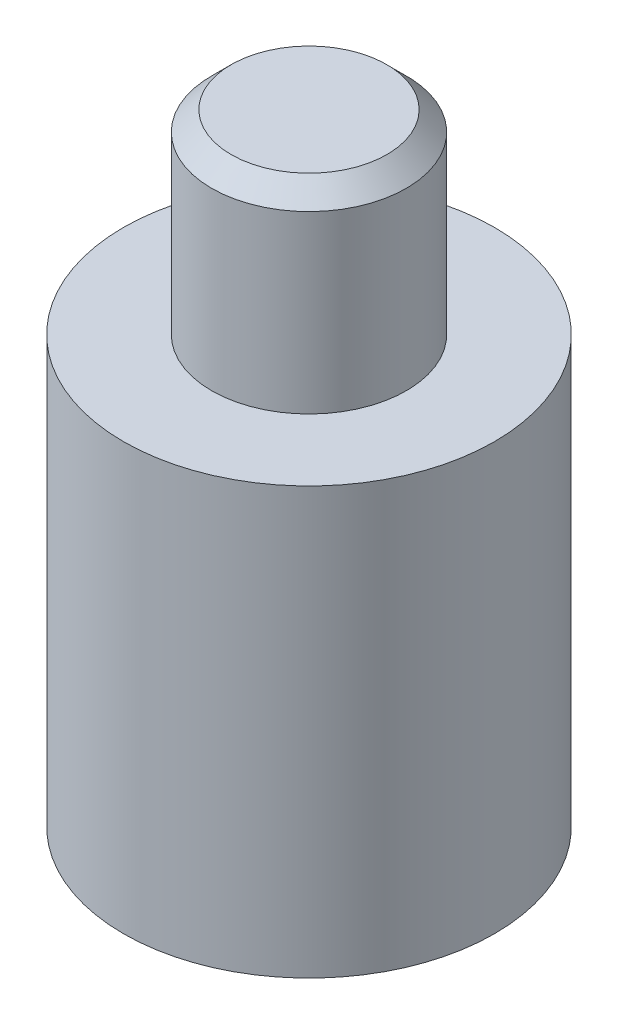
SolidWorks part; units mm, degrees
ref_plane "Front Plane" through (0, 0, 0) normal (0, 0, 1) x (1, 0, 0)
ref_plane "Top Plane" through (0, 0, 0) normal (0, 1, 0) x (1, 0, 0)
ref_plane "Right Plane" through (0, 0, 0) normal (1, 0, 0) x (0, 0, -1)
sketch "Sketch1" plane through (0, 0, 0) normal (0, 1, 0) x (1, 0, 0)
  circle A0 centre (0, 0) radius 1.5
  circle A1 centre (0, 0) radius 4.7625
extrude "Boss-Extrude1" add sketch "Sketch1" along normal blind 10.9409 contours A1 A0 | A0 region at (0, 0, 0) region at (-4.6278, 0, 0)
sketch "Sketch2" plane through (0, 10.9409, 0) normal (0, 1, 0) x (1, 0, 0)
  circle A0 centre (0, 0) radius 2.5
extrude "Boss-Extrude2" add sketch "Sketch2" along normal blind 5
extrude "Cut-Extrude1" cut sketch "Sketch1<3>" along normal blind 5 contours A0 region at (0, 0, 0)
sketch "Sketch1<3>" plane through (0, 0, 0) normal (0, 1, 0) x (1, 0, 0) same geometry as "Sketch1"
chamfer "Chamfer1" distance 0.5 angle 45 1 edges at (0, 15.9409, 2.5)
thread "Thread1" pitch 0.5 method extrude profile "Thread Profile1" start angle 0, offset 0, length 0, pitch 0.5, diameter 3
ref_plane "Plane1" through (1.5, 0, 0) normal (0, 0, 1) x (1, 0, 0)
sketch "Thread Profile1" plane through (1.5, 0, 0) normal (0, 0, 1) x (1, 0, 0)
  line L0 (0, 0) -> (0, 0.5) construction
  line L11 (0, 0) -> (0, 0.4375)
  line L12 (0, 0.4375) -> (-0.2706, 0.2812)
  line L13 (-0.2706, 0.2812) -> (-0.2706, 0.1562)
  line L15 (-0.2706, 0.1562) -> (0, 0)
  line L17 (-0.2706, 0.2187) -> (0, 0.2187) construction
  point P2 (0, 0)
  dimension "Pitch" = 0.5
  dimension "Profile_Angle" = 60
  dimension "Profile_Land" = 0.125
  dimension "Profile_Height" = 0.2706
